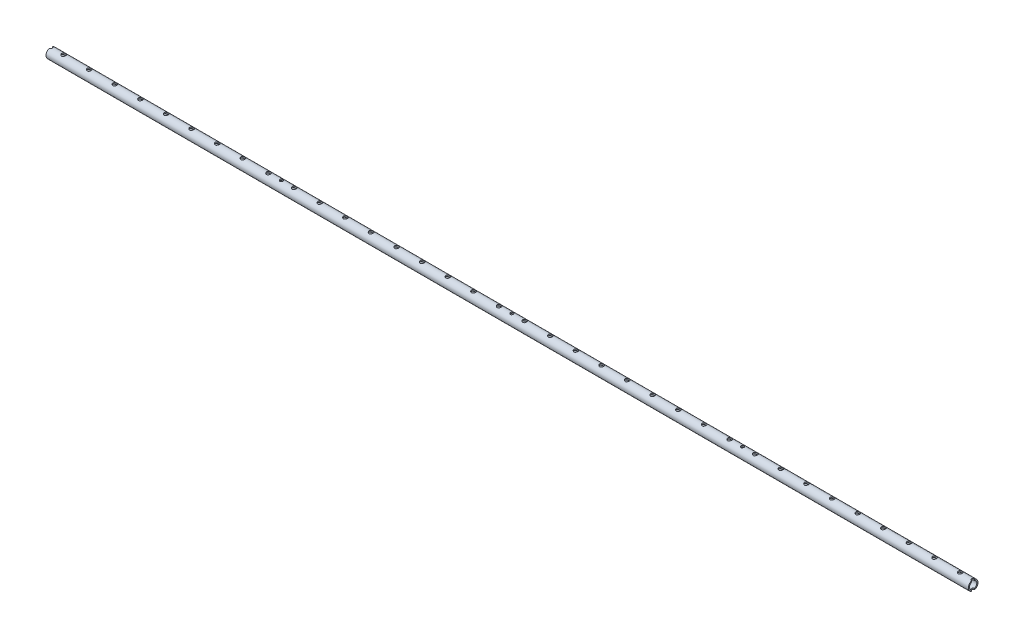
SolidWorks part; units mm, degrees
ref_plane "Front Plane" through (0, 0, 0) normal (0, 0, 1) x (1, 0, 0)
ref_plane "Top Plane" through (0, 0, 0) normal (0, 1, 0) x (1, 0, 0)
ref_plane "Right Plane" through (0, 0, 0) normal (1, 0, 0) x (0, 0, -1)
sketch "Sketch1" plane through (0, 0, 0) normal (1, 0, 0) x (0, 0, -1)
  circle A0 centre (0, 0) radius 9.525
  circle A1 centre (0, 0) radius 7.112
  dimension "D1" = 19.05
  dimension "D2" = 2.413
extrude "Boss-Extrude1" add sketch "Sketch1" along normal blind 1800
sketch "Sketch2" plane through (0, 0, 0) normal (0, 1, 0) x (1, 0, 0)
  line L0 (0, 0) -> (1800, 0) construction
  line L1 (0, 9.525) -> (0, -9.525) construction
  line L2 (1800, -9.525) -> (1800, 9.525) construction
  circle A0 centre (25, 0) radius 4
  circle A1 centre (75, 0) radius 4
  circle A2 centre (125, 0) radius 4
  circle A3 centre (175, 0) radius 4
  circle A4 centre (225, 0) radius 4
  circle A5 centre (275, 0) radius 4
  circle A6 centre (325, 0) radius 4
  circle A7 centre (375, 0) radius 4
  circle A8 centre (425, 0) radius 4
  circle A9 centre (475, 0) radius 4
  circle A10 centre (525, 0) radius 4
  circle A11 centre (575, 0) radius 4
  circle A12 centre (625, 0) radius 4
  circle A13 centre (675, 0) radius 4
  circle A14 centre (725, 0) radius 4
  circle A15 centre (775, 0) radius 4
  circle A16 centre (825, 0) radius 4
  circle A17 centre (875, 0) radius 4
  circle A18 centre (925, 0) radius 4
  circle A19 centre (975, 0) radius 4
  circle A20 centre (1025, 0) radius 4
  circle A21 centre (1075, 0) radius 4
  circle A22 centre (1125, 0) radius 4
  circle A23 centre (1175, 0) radius 4
  circle A24 centre (1225, 0) radius 4
  circle A25 centre (1275, 0) radius 4
  circle A26 centre (1325, 0) radius 4
  circle A27 centre (1375, 0) radius 4
  circle A28 centre (1425, 0) radius 4
  circle A29 centre (1475, 0) radius 4
  circle A30 centre (1525, 0) radius 4
  circle A31 centre (1575, 0) radius 4
  circle A32 centre (1625, 0) radius 4
  circle A33 centre (1675, 0) radius 4
  circle A34 centre (1725, 0) radius 4
  circle A35 centre (1775, 0) radius 4
  dimension "D1" = 8
  dimension "D2" = 25
  dimension "D4" = 50
  dimension "D3" = 36
extrude "Cut-Extrude1" cut sketch "Sketch2" along normal blind 20 contours A0 | A1 | A2 | A3 | A4 | A5 | A6 | A7 | A8 | A9 | A10 | A11 | A12 | A13 | A14 | A15 | A16 | A17 | A18 | A19 | A20 | A21 | A22 | A23 | A24 | A25 | A26 | A27 | A28 | A29 | A30 | A31 | A32 | A33 | A34 | A35
sketch "Sketch3" plane through (0, 0, 0) normal (0, 1, 0) x (1, 0, 0)
  line L0 (0, 0) -> (450, 0) construction
  line L3 (1800, -9.525) -> (1800, 9.525) construction
  circle A0 centre (450, 0) radius 3
  circle A2 centre (0, 0) radius 3
  circle A3 centre (1800, 0) radius 3
  circle A4 centre (900, 0) radius 3
  circle A5 centre (1350, 0) radius 3
  dimension "D1" = 6
  dimension "D3" = 3
  dimension "D2" = 450
extrude "Cut-Extrude2" cut sketch "Sketch3" against normal blind 20 and the other way blind 20 contours A2 | A0 | A3 | A4 | A5
